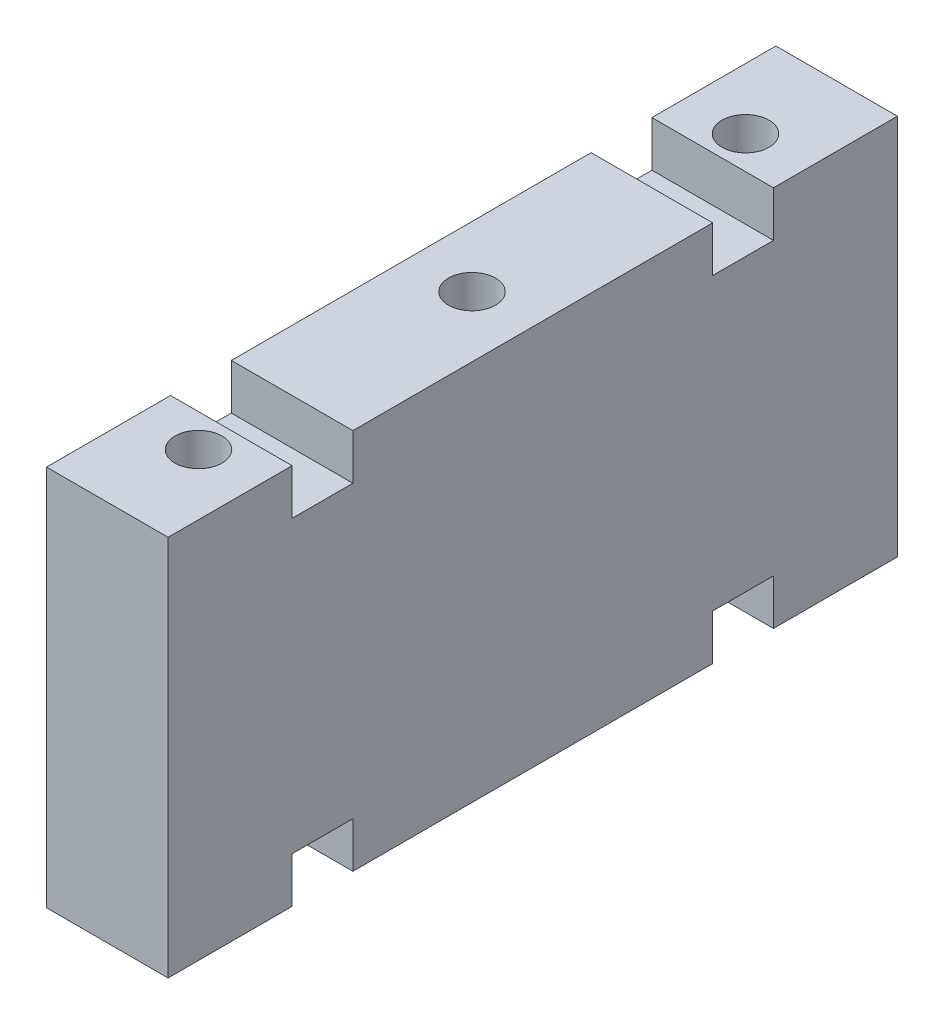
SolidWorks part; units mm, degrees
material "PET"
ref_plane "Front" through (0, 0, 0) normal (0, 0, 1) x (1, 0, 0)
ref_plane "Top" through (0, 0, 0) normal (0, 1, 0) x (1, 0, 0)
ref_plane "Right" through (0, 0, 0) normal (1, 0, 0) x (0, 0, -1)
sketch "Sketch1" plane through (0, 0, 0) normal (1, 0, 0) x (0, 0, -1)
  line L1 (-38.1, -19.939) -> (38.1, -19.939)
  line L2 (-38.1, -19.939) -> (-38.1, 19.939)
  line L3 (-38.1, 19.939) -> (38.1, 19.939)
  line L4 (38.1, -19.939) -> (38.1, 19.939)
  line L5 (-38.1, -19.939) -> (38.1, 19.939) construction
  line L6 (-38.1, 19.939) -> (38.1, -19.939) construction
  point P0 (0, 0)
  dimension "D1" = 39.878
  dimension "D2" = 76.2
extrude "Boss-Extrude1" add sketch "Sketch1" along normal blind 12.7
sketch "Sketch2" plane through (12.7, 0, 0) normal (1, 0, 0) x (0, 0, -1)
  line L0 (38.1, -19.939) -> (38.1, 19.939) construction
  line L1 (-25.146, 19.939) -> (-18.796, 19.939)
  line L2 (-25.146, 19.939) -> (-25.146, 15.1765)
  line L3 (-25.146, 15.1765) -> (-18.796, 15.1765)
  line L4 (-18.796, 19.939) -> (-18.796, 15.1765)
  line L5 (-25.146, 19.939) -> (-18.796, 15.1765) construction
  line L6 (-25.146, 15.1765) -> (-18.796, 19.939) construction
  line L7 (18.796, 19.939) -> (25.146, 19.939)
  line L8 (18.796, 19.939) -> (18.796, 15.1765)
  line L9 (18.796, 15.1765) -> (25.146, 15.1765)
  line L10 (25.146, 19.939) -> (25.146, 15.1765)
  line L11 (18.796, 19.939) -> (25.146, 15.1765) construction
  line L12 (18.796, 15.1765) -> (25.146, 19.939) construction
  line L13 (-25.146, -15.1765) -> (-18.796, -15.1765)
  line L14 (-25.146, -15.1765) -> (-25.146, -19.939)
  line L15 (-25.146, -19.939) -> (-18.796, -19.939)
  line L16 (-18.796, -15.1765) -> (-18.796, -19.939)
  line L17 (-25.146, -15.1765) -> (-18.796, -19.939) construction
  line L18 (-25.146, -19.939) -> (-18.796, -15.1765) construction
  line L19 (25.146, -19.939) -> (18.796, -19.939)
  line L20 (25.146, -19.939) -> (25.146, -15.1765)
  line L21 (25.146, -15.1765) -> (18.796, -15.1765)
  line L22 (18.796, -19.939) -> (18.796, -15.1765)
  line L23 (25.146, -19.939) -> (18.796, -15.1765) construction
  line L24 (25.146, -15.1765) -> (18.796, -19.939) construction
  line L27 (-38.1, 19.939) -> (-38.1, -19.939) construction
  line L29 (38.1, 19.939) -> (-38.1, 19.939) construction
  line L30 (-38.1, -19.939) -> (38.1, -19.939) construction
  point P0 (-21.971, 17.5578)
  point P5 (21.971, 17.5578)
  point P10 (-21.971, -17.5578)
  point P15 (21.971, -17.5578)
  dimension "D1" = 6.35
  dimension "D2" = 4.7625
  dimension "D3" = 12.954
  dimension "D6" = 12.954
extrude "Cut-Extrude1" cut sketch "Sketch2" against normal through all
sketch "Sketch5" plane through (0, 19.939, 0) normal (0, 1, 0) x (1, 0, 0)
  line L0 (12.7, -38.1) -> (0, -38.1) construction
  line L1 (12.7, 38.1) -> (0, 38.1) construction
  line L2 (6.35, -28.575) -> (6.35, 0) construction
  line L3 (6.35, 0) -> (6.35, 28.575) construction
  line L5 (6.35, 28.575) -> (0, 28.575) construction
  line L6 (0, 38.1) -> (0, 25.146) construction
  line L8 (6.35, 28.575) -> (12.7, 28.575) construction
  line L9 (12.7, 38.1) -> (12.7, 25.146) construction
  point P1 (6.35, 28.575)
  point P3 (6.35, 0)
  point P5 (6.35, -28.575)
  dimension "D1" = 9.525
  dimension "D2" = 9.525
hole_wizard "#10 (0.1935) Diameter Hole1" positions "Sketch5" profile "Sketch4" hole size "#10" standard "ANSI Inch" end condition up to next
sketch "Sketch4" plane through (6.35, 19.939, -28.575) normal (1, 0, 0) x (0, 0, 1)
  line L0 (0, 0) -> (0, 39.878)
  line L1 (0, 39.878) -> (2.4574, 39.878)
  line L2 (2.4574, 39.878) -> (2.4574, 0)
  line L5 (2.4574, 0) -> (0, 0)
  line L11 (0, -6.35) -> (0, 107.95) construction
  dimension "Thru Hole Dia." = 4.9149
  dimension "Thru Hole Depth" = 39.878
